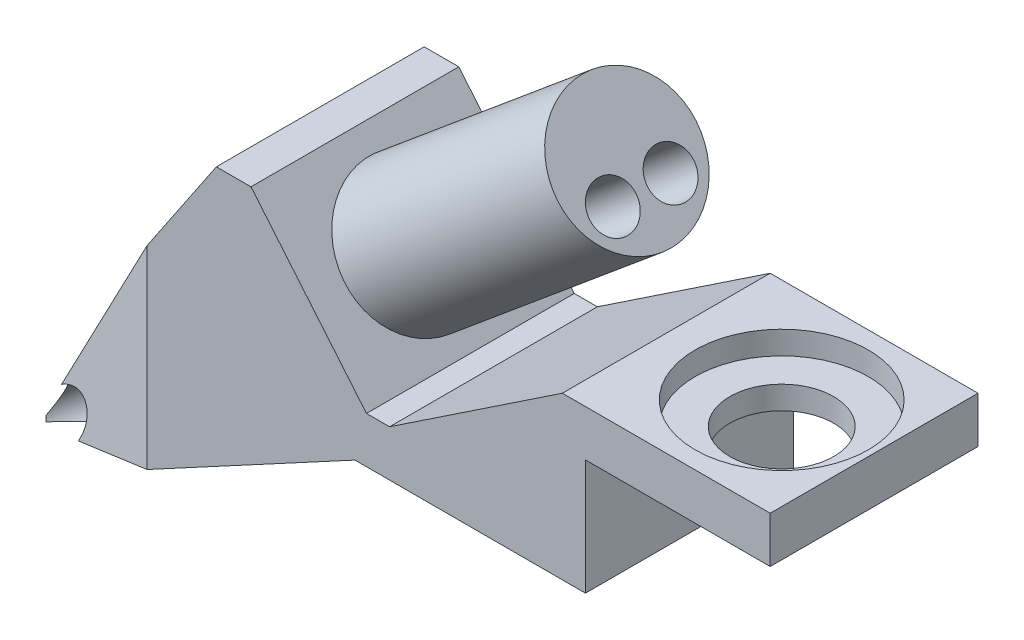
SolidWorks part; units mm, degrees
ref_plane "Front Plane" through (0, 0, 0) normal (0, 0, 1) x (1, 0, 0)
ref_plane "Top Plane" through (0, 0, 0) normal (0, 1, 0) x (1, 0, 0)
ref_plane "Right Plane" through (0, 0, 0) normal (1, 0, 0) x (0, 0, -1)
sketch "Sketch1" plane through (0, 0, 0) normal (0, 0, 1) x (1, 0, 0)
  line L0 (0, 0) -> (17.6167, 9.5)
  line L1 (17.6167, 9.5) -> (27.6, 9.5)
  line L2 (27.6, 9.5) -> (27.6, 14.5)
  line L3 (27.6, 14.5) -> (35.6, 14.5)
  line L4 (35.6, 14.5) -> (35.6, 16.5)
  line L5 (35.6, 16.5) -> (26.6, 16.5)
  line L8 (11.6167, 17.5) -> (0, 0.25)
  line L10 (18.1167, 11.5) -> (13.1167, 17.5)
  line L11 (13.1167, 17.5) -> (11.6167, 17.5)
  line L12 (26.6, 16.5) -> (19.1167, 11.5)
  line L13 (19.1167, 11.5) -> (18.1167, 11.5)
  line L14 (0, 0) -> (0, 0.25)
  dimension "D1" = 35.6
  dimension "D2" = 9.5
  dimension "D3" = 14.5
  dimension "D4" = 17.5
  dimension "D5" = 2
  dimension "D6" = 8
  dimension "D7" = 2
  dimension "D8" = 1.5
  dimension "D9" = 0.5
  dimension "D10" = 1
  dimension "D11" = 1
  dimension "D12" = 5
  dimension "D13" = 9
  dimension "D14" = 0.25
extrude "Boss-Extrude1" add sketch "Sketch1" along normal blind 9
sketch "Sketch2" plane through (0, 16.5, 0) normal (0, 1, 0) x (1, 0, 0)
  line L0 (35.6, -9) -> (35.6, 0) construction
  line L1 (8.6167, 0) -> (0, 0)
  line L2 (0, 0) -> (0, -4)
  line L3 (0, -4) -> (8.6167, 0)
  line L4 (0, -5) -> (0, -9)
  line L5 (0, -9) -> (8.6167, -9)
  line L6 (0, -9) -> (0, 0) construction
  line L7 (11.6167, 0) -> (0, 0) construction
  line L8 (0, -5) -> (8.6167, -9)
  line L9 (11.6167, -9) -> (0, -9) construction
  line L10 (11.6167, -9) -> (11.6167, 0) construction
  circle A0 centre (31.6, -4.5) radius 2.25
  circle A1 centre (31.6, -4.5) radius 3.75
  point P5 (35.6, -4.5)
  point P19 (0, -4.5)
  dimension "D3" = 4.5
  dimension "D5" = 7.5
  dimension "D1" = 4
  dimension "D2" = 1
  dimension "D4" = 3
  dimension "D6" = 0.5
extrude "Cut-Extrude1" cut sketch "Sketch2" against normal up to vertex (16.5 mm away) contours A0 | L2 L3 L1 | L8 L4 L5 region at (2.8722, 16.5, 1.3333) region at (2.8722, 16.5, 7.6667) region at (31.6, 16.5, 4.5) up to point (0, 0, 9)
extrude "Cut-Extrude2" cut sketch "Sketch2<3>" against normal blind 1 contours A1 A0 region at (27.9561, 16.5, 4.5)
sketch "Sketch2<3>" plane through (0, 16.5, 0) normal (0, 1, 0) x (1, 0, 0) same geometry as "Sketch2"
sketch "Sketch3" plane through (16.3476, 13.623, 0) normal (0.7682, 0.6402, 0) x (0, 0, -1)
  line L0 (-9, 5.0468) -> (0, 5.0468) construction
  circle A0 centre (-4.5, 1.0468) radius 3
  point P4 (-4.5, 5.0468)
  dimension "D1" = 6
  dimension "D2" = 4
extrude "Boss-Extrude2" add sketch "Sketch3" along normal blind 12
sketch "Sketch4" plane through (16.3476, 13.623, 0) normal (0.7682, 0.6402, 0) x (0, 0, -1)
  line L0 (-5.75, 0.0468) -> (-3.25, 0.0468) construction
  line L1 (-4.5, 4.0468) -> (-4.5, -1.9532) construction
  line L2 (-7.5, 1.0468) -> (-1.5, 1.0468) construction
  circle A0 centre (-5.75, 0.0468) radius 1
  circle A1 centre (-3.25, 0.0468) radius 1
  circle A2 centre (-4.5, 1.0468) radius 3 construction
  circle A3 centre (-4.5, 1.0468) radius 3 construction
  point P13 (-4.5, 0.0468)
  dimension "D1" = 2
  dimension "D2" = 2.5
  dimension "D3" = 1
extrude "Cut-Extrude3" cut sketch "Sketch4" against normal through all both and the other way through all
equation "\"D6@Sketch2\"=\"D2@Sketch2\"/2"
